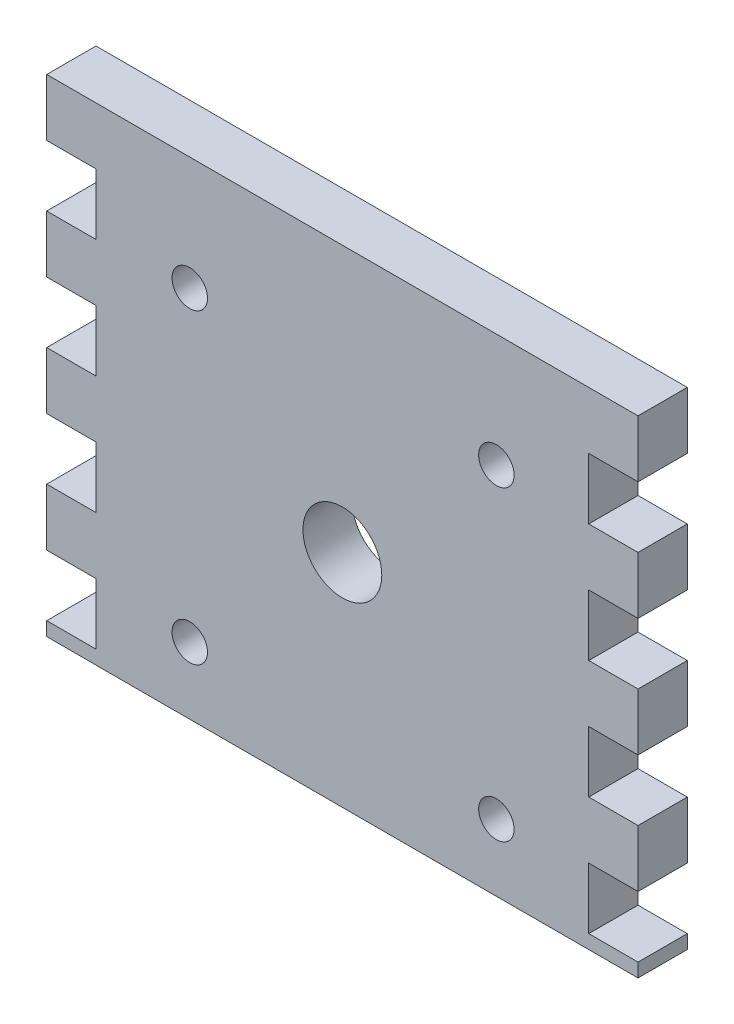
SolidWorks part; units mm, degrees
ref_plane "Front Plane" through (0, 0, 0) normal (0, 0, 1) x (1, 0, 0)
ref_plane "Top Plane" through (0, 0, 0) normal (0, 1, 0) x (1, 0, 0)
ref_plane "Right Plane" through (0, 0, 0) normal (1, 0, 0) x (0, 0, -1)
sketch "Sketch1" plane through (0, 0, 0) normal (0, 0, 1) x (1, 0, 0)
  line L1 (-37.8801, 17.0433) -> (38.3199, 17.0433)
  line L2 (-37.8801, 17.0433) -> (-37.8801, -59.1567)
  line L3 (-37.8801, -59.1567) -> (38.3199, -59.1567)
  line L4 (38.3199, 17.0433) -> (38.3199, -59.1567)
  dimension "D1" = 76.2
  dimension "D2" = 76.2
extrude "Boss-Extrude1" add sketch "Sketch1" along normal blind 6.35
sketch "Sketch2" plane through (0, 0, 6.35) normal (0, 0, 1) x (1, 0, 0)
  line L0 (-37.8801, 17.0433) -> (-31.5301, 17.0433)
  line L1 (38.3199, 17.0433) -> (-37.8801, 17.0433) construction
  line L2 (-31.5301, 17.0433) -> (-31.5301, 9.4233)
  line L3 (-31.5301, 9.4233) -> (-37.8801, 9.4233)
  line L4 (-37.8801, 17.0433) -> (-37.8801, -59.1567) construction
  line L5 (-37.8801, 9.4233) -> (-37.8801, 1.8033)
  line L6 (-37.8801, 1.8033) -> (-31.5301, 1.8033)
  line L7 (-31.5301, 1.8033) -> (-31.5301, -5.8167)
  line L8 (-31.5301, -5.8167) -> (-37.8801, -5.8167)
  line L9 (-37.8801, -5.8167) -> (-37.8801, -13.4367)
  line L10 (-37.8801, -13.4367) -> (-31.5301, -13.4367)
  line L11 (-31.5301, -13.4367) -> (-31.5301, -21.0567)
  line L12 (-31.5301, -21.0567) -> (-37.8801, -21.0567)
  line L13 (-37.8801, -21.0567) -> (-46.7258, -21.0567)
  line L14 (-37.8801, -21.0567) -> (-37.8801, -28.6767) [skipped]
  line L15 (-46.7258, -21.0567) -> (-46.7258, 17.0433)
  line L16 (-46.7258, 17.0433) -> (-37.8801, 17.0433)
  line L19 (47.1657, -21.0567) -> (47.1657, 17.0433)
  line L20 (38.3199, -21.0567) -> (47.1657, -21.0567)
  line L21 (31.9699, -21.0567) -> (38.3199, -21.0567)
  line L22 (31.9699, -13.4367) -> (31.9699, -21.0567)
  line L23 (38.3199, -13.4367) -> (31.9699, -13.4367)
  line L24 (38.3199, -5.8167) -> (38.3199, -13.4367)
  line L25 (31.9699, -5.8167) -> (38.3199, -5.8167)
  line L26 (31.9699, 1.8033) -> (31.9699, -5.8167)
  line L27 (38.3199, 1.8033) -> (31.9699, 1.8033)
  line L28 (38.3199, 9.4233) -> (38.3199, 1.8033)
  line L29 (31.9699, 9.4233) -> (38.3199, 9.4233)
  line L30 (31.9699, 17.0433) -> (31.9699, 9.4233)
  line L31 (38.3199, 17.0433) -> (31.9699, 17.0433)
  line L32 (47.1657, 17.0433) -> (38.3199, 17.0433)
  dimension "D1" = 7.62
  dimension "D2" = 7.62
  dimension "D3" = 6.35
  dimension "D4" = 6.35
  dimension "D6" = 38.1
  dimension "D5" = 3
extrude "Cut-Extrude1" cut sketch "Sketch2" against normal blind 6.35
sketch "Sketch3" plane through (0, 0, 6.35) normal (0, 0, 1) x (1, 0, 0)
  line L1 (-31.5301, -21.0567) -> (-37.8801, -21.0567)
  line L2 (-31.5301, -21.0567) -> (-31.5301, -59.1567)
  line L3 (-31.5301, -59.1567) -> (-37.8801, -59.1567)
  line L4 (-37.8801, -21.0567) -> (-37.8801, -59.1567)
  line L5 (31.9699, -21.0567) -> (38.3199, -21.0567)
  line L6 (31.9699, -21.0567) -> (31.9699, -59.1567)
  line L7 (31.9699, -59.1567) -> (38.3199, -59.1567)
  line L8 (38.3199, -21.0567) -> (38.3199, -59.1567)
extrude "Cut-Extrude2" cut sketch "Sketch3" against normal blind 6.35
sketch "Sketch4" plane through (0, 0, 6.35) normal (0, 0, 1) x (1, 0, 0)
  line L0 (-31.5301, -13.4367) -> (-31.5301, -21.0567)
  line L1 (-31.5301, -59.1567) -> (-31.5301, -13.4367) construction
  line L2 (-31.5301, -21.0567) -> (-37.8801, -21.0567)
  line L3 (-37.8801, -21.0567) -> (-37.8801, -28.6767)
  line L4 (-37.8801, -28.6767) -> (-31.5301, -28.6767)
  line L5 (-31.5301, -21.0567) -> (-31.5301, -28.6767)
  line L6 (0.2199, 17.0433) -> (0.2199, -59.1567)
  line L7 (31.9699, 17.0433) -> (-31.5301, 17.0433) construction
  line L8 (-31.5301, -59.1567) -> (31.9699, -59.1567) construction
  line L9 (31.9699, -21.0567) -> (38.3199, -21.0567)
  line L10 (38.3199, -21.0567) -> (38.3199, -28.6767)
  line L11 (38.3199, -28.6767) -> (31.9699, -28.6767)
  line L12 (31.9699, -21.0567) -> (31.9699, -28.6767)
  line M6 (-31.5301, -13.4367) -> (-31.5301, -59.1567)
  line M8 (31.9699, -59.1567) -> (31.9699, -13.4367)
  dimension "D1" = 7.62
  dimension "D2" = 7.62
  dimension "D3" = 6.35
  dimension "D4" = 6.35
extrude "Boss-Extrude3" add sketch "Sketch4" against normal blind 6.35 contours L3 L4 L2 M6 | L11 L10 L9 M8 region at (-34.7051, -24.8667, 6.35) region at (35.1449, -24.8667, 6.35)
sketch "Sketch5" plane through (0, 17.0433, 0) normal (0, 1, 0) x (1, 0, 0)
  line L1 (-31.5301, 0) -> (31.9699, 0)
  line L2 (-31.5301, 0) -> (-31.5301, -6.35)
  line L3 (-31.5301, -6.35) -> (31.9699, -6.35)
  line L4 (31.9699, 0) -> (31.9699, -6.35)
extrude "Cut-Extrude3" cut sketch "Sketch5" against normal blind 7.62
sketch "Sketch6" plane through (0, 0, 6.35) normal (0, 0, 1) x (1, 0, 0)
  line L0 (-31.5301, -59.1567) -> (31.9699, -59.1567) construction
  line L1 (-19.4468, -5.1999) -> (0.2199, -24.8667) construction
  line L2 (0.2199, -24.8667) -> (-37.8801, -24.8667) construction
  line L3 (31.9699, -28.6767) -> (31.9699, -59.1567) construction
  circle A0 centre (0.2199, -24.8667) radius 5.08
  circle A5 centre (-19.4468, -5.1999) radius 2.286
  circle A6 centre (20.0663, -5.1999) radius 2.286
  circle A7 centre (20.0663, -44.7131) radius 2.286
  circle A8 centre (-19.4468, -44.7131) radius 2.286
  point P16 (0.2825, -24.9292)
  point P18 (0.3097, -24.9565)
  dimension "D3" = 10.16
  dimension "D6" = 4
  dimension "D8" = 4.572
  dimension "D1" = 34.29
  dimension "D2" = 31.75
  dimension "D4" = 45
  dimension "D5" = 27.813
extrude "Cut-Extrude4" cut sketch "Sketch6" against normal through all
sketch "Sketch7" plane through (0, 0, 6.35) normal (0, 0, 1) x (1, 0, 0)
  line L0 (-31.5301, -28.6767) -> (-31.5301, -36.2967)
  line L1 (-31.5301, -59.1567) -> (-31.5301, -28.6767) construction
  line L2 (-31.5301, -36.2967) -> (-37.8801, -36.2967)
  line L3 (31.9699, -28.6767) -> (31.9699, -36.2967)
  line L4 (31.9699, -28.6767) -> (31.9699, -59.1567) construction
  line L5 (31.9699, -36.2967) -> (38.3199, -36.2967)
  line L6 (-37.8801, -36.2967) -> (-37.8801, -43.9167)
  line L7 (-37.8801, -43.9167) -> (-31.5301, -43.9167)
  line L8 (38.3199, -36.2967) -> (38.3199, -43.9167)
  line L9 (38.3199, -43.9167) -> (31.9699, -43.9167)
  line L12 (-31.5301, -43.9167) -> (-31.5301, -59.1567)
  line M27 (-31.5301, -28.6767) -> (-31.5301, -59.1567)
  line M29 (31.9699, -59.1567) -> (31.9699, -28.6767)
  dimension "D1" = 7.62
  dimension "D2" = 6.35
  dimension "D3" = 7.62
  dimension "D4" = 6.35
  dimension "D5" = 7.62
  dimension "D6" = 7.62
  dimension "D7" = 6.35
  dimension "D8" = 6.35
extrude "Boss-Extrude4" add sketch "Sketch7" against normal blind 6.35 contours L6 L7 L2 M27 | L9 L8 L5 M29 region at (-34.7051, -40.1067, 6.35) region at (35.1449, -40.1067, 6.35)
sketch "Sketch8" plane through (0, 0, 6.35) normal (0, 0, 1) x (1, 0, 0)
sketch "Sketch9" plane through (0, 0, 6.35) normal (0, 0, 1) x (1, 0, 0)
  line L0 (-31.5301, -43.9167) -> (-31.5301, -59.1567)
  line L1 (-31.5301, -59.1567) -> (31.9699, -59.1567)
  line L2 (31.9699, -59.1567) -> (31.9699, -43.9167)
  line L3 (31.9699, -43.9167) -> (31.9699, -59.1567) construction
  line L6 (-31.5301, -53.3208) -> (31.9699, -53.3208)
  line L7 (-31.5301, -53.3208) -> (-31.5301, -59.1567)
  line L8 (-31.5301, -59.1567) -> (31.9699, -59.1567)
  line L9 (31.9699, -53.3208) -> (31.9699, -59.1567)
  line M28 (-31.5301, -59.1567) -> (31.9699, -59.1567)
  line M29 (31.9699, -59.1567) -> (31.9699, -43.9167)
extrude "Cut-Extrude5" cut sketch "Sketch9" against normal blind 6.35 contours L6 L0 M28 M29 region at (0.2199, -56.2388, 6.35)
sketch "Sketch10" plane through (0, 1.8033, 0) normal (0, -1, 0) x (1, 0, 0)
  line L0 (38.3199, 0) -> (38.3199, 6.35) construction
  line L1 (31.9699, 0) -> (38.3199, 0)
  line L2 (31.9699, 0) -> (31.9699, 6.35)
  line L3 (31.9699, 6.35) -> (38.3199, 6.35)
  line L4 (38.3199, 0) -> (38.3199, 6.35)
  line L5 (38.3199, 6.35) -> (31.9699, 6.35) construction
  point P9 (31.9699, 0)
  point P10 (31.9699, 0)
extrude "Boss-Extrude5" add sketch "Sketch10" along normal blind 55.118
sketch "Sketch11" plane through (0, 1.8033, 0) normal (0, -1, 0) x (1, 0, 0)
  line L1 (-31.5301, 0) -> (-37.8801, 0)
  line L2 (-31.5301, 0) -> (-31.5301, 6.35)
  line L3 (-31.5301, 6.35) -> (-37.8801, 6.35)
  line L4 (-37.8801, 0) -> (-37.8801, 6.35)
extrude "Boss-Extrude6" add sketch "Sketch11" along normal blind 55.118
sketch "Sketch12" plane through (0, 0, 6.35) normal (0, 0, 1) x (1, 0, 0)
  line L0 (-37.8801, 9.4233) -> (-37.8801, 2.0573)
  line L1 (-37.8801, 9.4233) -> (-37.8801, -53.3147) construction
  line L2 (-37.8801, 2.0573) -> (-31.5301, 2.0573)
  line L3 (-31.5301, 2.0573) -> (-31.5301, -5.8167)
  line L4 (-31.5301, -5.8167) -> (-37.8801, -5.8167)
  line L5 (-37.8801, -5.8167) -> (-37.8801, -13.1827)
  line L6 (-37.8801, -13.1827) -> (-31.5301, -13.1827)
  line L7 (-31.5301, -13.1827) -> (-31.5301, -21.0567)
  line L8 (-31.5301, -21.0567) -> (-37.8801, -21.0567)
  line L9 (-37.8801, -21.0567) -> (-37.8801, -28.4227)
  line L10 (-37.8801, -28.4227) -> (-31.5301, -28.4227)
  line L11 (-31.5301, -28.4227) -> (-31.5301, -36.2967)
  line L12 (-31.5301, -36.2967) -> (-37.8801, -36.2967)
  line L13 (-37.8801, -36.2967) -> (-37.8801, -43.6627)
  line L14 (-37.8801, -43.6627) -> (-31.5301, -43.6627)
  line L15 (-31.5301, -43.6627) -> (-31.5301, -51.5367)
  line L16 (-31.5301, -51.5367) -> (-37.8801, -51.5367)
  line L17 (-37.8801, 9.4233) -> (-56.0123, 9.4233)
  line L18 (-56.0123, 9.4233) -> (-56.0123, -53.8176)
  line L19 (-56.0123, -53.8176) -> (-37.8801, -51.5367)
  line L20 (0.2199, 9.4233) -> (0.2199, -53.3208)
  line L21 (-37.8801, 9.4233) -> (38.3199, 9.4233) construction
  line L22 (-31.5301, -53.3208) -> (31.9699, -53.3208) construction
  line L23 (56.4521, 9.4233) -> (56.4521, -53.8176)
  line L24 (38.3199, 9.4233) -> (56.4521, 9.4233)
  line L25 (38.3199, 9.4233) -> (38.3199, 2.0573)
  line L26 (38.3199, 2.0573) -> (31.9699, 2.0573)
  line L27 (31.9699, 2.0573) -> (31.9699, -5.8167)
  line L28 (31.9699, -5.8167) -> (38.3199, -5.8167)
  line L29 (38.3199, -5.8167) -> (38.3199, -13.1827)
  line L30 (38.3199, -13.1827) -> (31.9699, -13.1827)
  line L31 (31.9699, -13.1827) -> (31.9699, -21.0567)
  line L32 (31.9699, -21.0567) -> (38.3199, -21.0567)
  line L33 (38.3199, -21.0567) -> (38.3199, -28.4227)
  line L34 (38.3199, -28.4227) -> (31.9699, -28.4227)
  line L35 (31.9699, -28.4227) -> (31.9699, -36.2967)
  line L36 (31.9699, -36.2967) -> (38.3199, -36.2967)
  line L37 (38.3199, -36.2967) -> (38.3199, -43.6627)
  line L38 (38.3199, -43.6627) -> (31.9699, -43.6627)
  line L39 (31.9699, -43.6627) -> (31.9699, -51.5367)
  line L40 (31.9699, -51.5367) -> (38.3199, -51.5367)
  line L41 (56.4521, -53.8176) -> (38.3199, -51.5367)
  line M26 (38.3199, -53.3147) -> (38.3199, 9.4233)
  line M28 (-37.8801, 9.4233) -> (-37.8801, -53.3147)
  dimension "D1" = 7.366
  dimension "D2" = 7.874
  dimension "D3" = 6.35
  dimension "D4" = 4
extrude "Cut-Extrude7" cut sketch "Sketch12" against normal blind 55.118 contours L18 L19 L17 M28 | L41 L23 L24 M26 | L39 L40 L38 M26 | L35 L36 L34 M26 | L31 L32 L30 M26 | L27 L28 L26 M26 | L4 L3 L2 M28 | L8 L7 L6 M28 | L12 L11 L10 M28 | L16 L15 L14 M28 region at (-47.0017, -21.6304, 6.35) region at (-34.7051, -1.8797, 6.35) region at (-34.7051, -17.1197, 6.35) region at (-34.7051, -47.5997, 6.35) region at (-34.7051, -32.3597, 6.35) region at (47.4415, -21.6304, 6.35) region at (35.1449, -47.5997, 6.35) region at (35.1449, -1.8797, 6.35) region at (35.1449, -32.3597, 6.35) region at (35.1449, -17.1197, 6.35)
